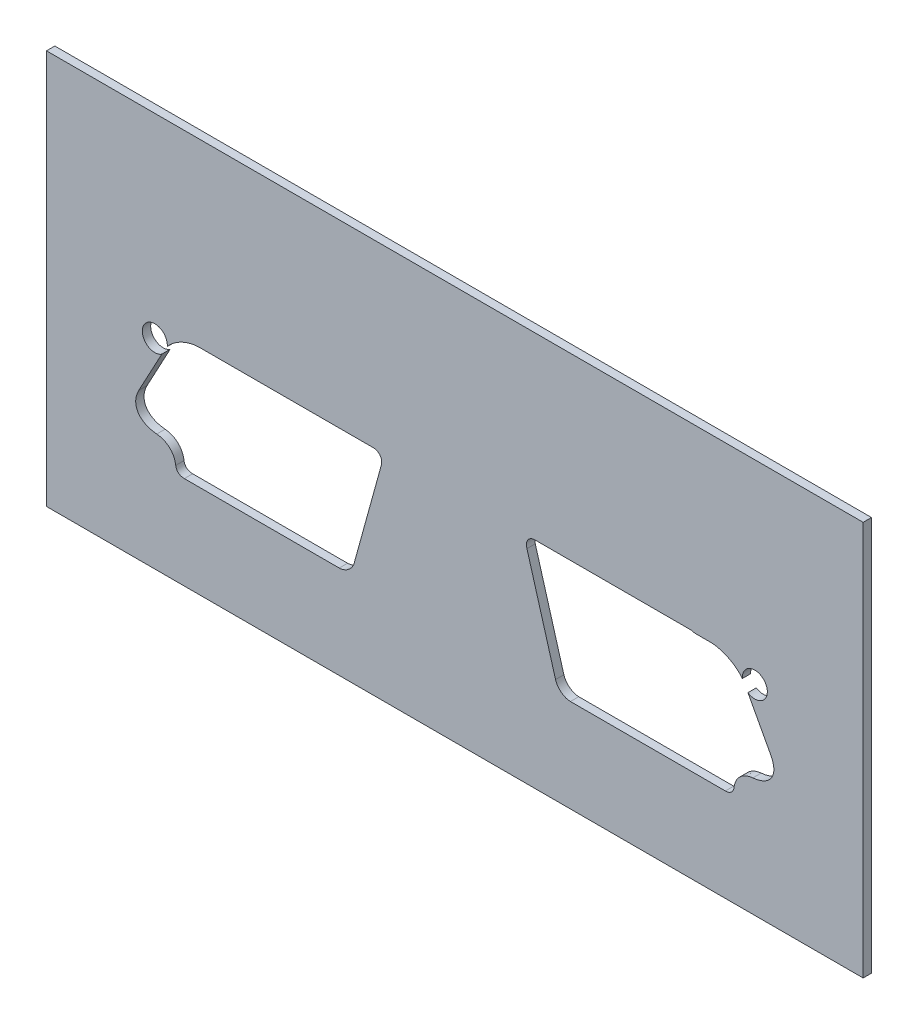
SolidWorks part; units mm, degrees
ref_plane "Спереди" through (0, 0, 0) normal (0, 0, 1) x (1, 0, 0)
ref_plane "Сверху" through (0, 0, 0) normal (0, 1, 0) x (1, 0, 0)
ref_plane "Справа" through (0, 0, 0) normal (1, 0, 0) x (0, 0, -1)
sketch "Эскиз1" plane through (0, 0, 0) normal (0, 0, 1) x (1, 0, 0)
  line L1 (-49, 5.8392) -> (-49, -22.5167)
  line L2 (-49, -22.5167) -> (49, -22.5167)
  line L3 (49, 5.8392) -> (49, -22.5167)
  line L6 (49, 26.4822) -> (49, 5.1962) construction
  line L8 (-49, 5.8392) -> (-49, 15.8392)
  line L9 (-49, 15.8392) -> (49, 15.8392)
  line L10 (49, 5.8392) -> (49, 15.8392)
extrude "Бобышка-Вытянуть1" add sketch "Эскиз1" along normal blind 1
sketch "Эскиз2" plane through (0, 0, 0) normal (0, 0, -1) x (-1, 0, 0)
  line L0 (27.2261, -9.1221) -> (15.7399, -9.1221)
  line L1 (14.9178, -10.1567) -> (17.4421, -18.9309)
  line L2 (19.1226, -20.331) -> (30.8268, -20.331)
  line L3 (31.6433, -19.2954) -> (29.101, -10.4886)
  line L4 (0, 0) -> (0, -19.7017) construction
  line L5 (-31.6433, -19.2954) -> (-29.101, -10.4886)
  line L6 (-19.1226, -20.331) -> (-30.8268, -20.331)
  line L7 (-14.9178, -10.1567) -> (-17.4421, -18.9309)
  line L8 (-27.2261, -9.1221) -> (-15.7399, -9.1221)
  arc A0 (15.7399, -9.1221) -> (14.9178, -10.1567) centre (15.8146, -10.0254) ccw
  arc A1 (17.4421, -18.9309) -> (19.1226, -20.331) centre (19.2232, -18.5017) ccw
  arc A2 (30.8268, -20.331) -> (31.6433, -19.2954) centre (30.7494, -19.4304) ccw
  arc A3 (29.101, -10.4886) -> (27.2261, -9.1221) centre (27.3312, -10.9473) ccw
  arc A4 (-29.101, -10.4886) -> (-27.2261, -9.1221) centre (-27.3312, -10.9473) cw
  arc A5 (-30.8268, -20.331) -> (-31.6433, -19.2954) centre (-30.7494, -19.4304) cw
  arc A6 (-17.4421, -18.9309) -> (-19.1226, -20.331) centre (-19.2232, -18.5017) cw
  arc A7 (-15.7399, -9.1221) -> (-14.9178, -10.1567) centre (-15.8146, -10.0254) cw
extrude "Вырез-Вытянуть4" cut sketch "Эскиз2" against normal through all
sketch "Эскиз4" plane through (0, 0, 0) normal (0, 0, -1) x (-1, 0, 0)
  circle A0 centre (36, -7.525) radius 1.5
  circle A1 centre (-36, -7.525) radius 1.5
extrude "Вырез-Вытянуть5" cut sketch "Эскиз4" against normal through all
sketch "Sketch3" plane through (0, 0, 1) normal (0, 0, 1) x (1, 0, 0)
  line L4 (-35.1709, -8.775) -> (-37.9251, -13.9067)
  line L5 (8.6523, -7.0681) -> (12.0857, -18.9615)
  line L6 (28.2287, -5.6825) -> (9.638, -5.6825)
  line L7 (30.6309, -5.7832) -> (28.7783, -5.7839)
  line L8 (37.9106, -13.8798) -> (35.1709, -8.775)
  line L9 (13.8713, -20.3472) -> (32.462, -20.3472)
  line L10 (8.6523, -7.0681) -> (12.0857, -18.9615)
  line L11 (28.2287, -5.6825) -> (9.638, -5.6825)
  line L12 (30.6309, -5.7832) -> (28.7783, -5.7839)
  line L13 (37.9106, -13.8798) -> (35.1709, -8.775)
  line L14 (13.8713, -20.3472) -> (32.462, -20.3472)
  line L15 (-9.8219, -5.7989) -> (-30.645, -5.807)
  line L16 (-12.0807, -18.9439) -> (-8.8308, -7.1669)
  line L17 (-32.462, -20.3472) -> (-13.8713, -20.3472)
  line L18 (-35.1709, -8.775) -> (-37.9251, -13.9067)
  line L19 (-9.8219, -5.7989) -> (-30.645, -5.807)
  line L20 (-12.0807, -18.9439) -> (-8.8308, -7.1669)
  line L21 (-32.462, -20.3472) -> (-13.8713, -20.3472)
  arc A2 (34.5043, -7.6389) -> (34.5716, -7.9829) centre (36, -7.525) ccw
  arc A3 (34.5716, -7.9829) -> (35.1709, -8.775) centre (36, -7.525) ccw
  arc A4 (34.5043, -7.6389) -> (34.5716, -7.9829) centre (36, -7.525) ccw
  arc A5 (34.5716, -7.9829) -> (35.1709, -8.775) centre (36, -7.525) ccw
  arc A6 (-35.1709, -8.775) -> (-34.5791, -8.0058) centre (-36, -7.525) ccw
  arc A7 (-34.5791, -8.0058) -> (-34.5051, -7.6482) centre (-36, -7.525) ccw
  arc A8 (-35.1709, -8.775) -> (-34.5791, -8.0058) centre (-36, -7.525) ccw
  arc A9 (-34.5791, -8.0058) -> (-34.5051, -7.6482) centre (-36, -7.525) ccw
  ellipse E5 centre (10.038, -7.0681) end of major axis (8.8285, -6.0207) minor radius 1.2 (9.638, -5.6825) -> (8.6523, -7.0681) ccw
  ellipse E6 centre (28.6287, -7.0681) end of major axis (27.4192, -6.0207) minor radius 1.2 (28.7783, -5.7839) -> (28.2287, -5.6825) ccw
  ellipse E7 centre (31.8702, -8.0919) end of major axis (28.7995, -6.6629) minor radius 2 (34.5043, -7.6389) -> (30.6309, -5.7832) ccw
  ellipse E8 centre (32.062, -18.9615) end of major axis (30.8525, -17.9141) minor radius 1.2 (32.462, -20.3472) -> (33.4962, -19.4843) ccw
  ellipse E9 centre (13.4713, -18.9615) end of major axis (12.2618, -17.9141) minor radius 1.2 (12.0857, -18.9615) -> (13.8713, -20.3472) ccw
  ellipse E10 centre (10.038, -7.0681) end of major axis (8.8285, -6.0207) minor radius 1.2 (9.638, -5.6825) -> (8.6523, -7.0681) ccw
  ellipse E11 centre (28.6287, -7.0681) end of major axis (27.4192, -6.0207) minor radius 1.2 (28.7783, -5.7839) -> (28.2287, -5.6825) ccw
  ellipse E12 centre (31.8702, -8.0919) end of major axis (28.7995, -6.6629) minor radius 2 (34.5043, -7.6389) -> (30.6309, -5.7832) ccw
  ellipse E13 centre (32.062, -18.9615) end of major axis (30.8525, -17.9141) minor radius 1.2 (32.462, -20.3472) -> (33.4962, -19.4843) ccw
  ellipse E14 centre (13.4713, -18.9615) end of major axis (12.2618, -17.9141) minor radius 1.2 (12.0857, -18.9615) -> (13.8713, -20.3472) ccw
  ellipse E15 centre (-31.8835, -8.1166) end of major axis (-28.8122, -6.6856) minor radius 2 (-30.645, -5.807) -> (-34.5051, -7.6482) ccw
  ellipse E16 centre (-10.2214, -7.1846) end of major axis (-9.0119, -6.1371) minor radius 1.2 (-8.8308, -7.1669) -> (-9.8219, -5.7989) ccw
  ellipse E17 centre (-13.4713, -18.9615) end of major axis (-12.2618, -17.9141) minor radius 1.2 (-13.8713, -20.3472) -> (-12.0807, -18.9439) ccw
  ellipse E18 centre (-32.062, -18.9615) end of major axis (-30.8525, -17.9141) minor radius 1.2 (-33.4952, -19.4922) -> (-32.462, -20.3472) ccw
  ellipse E19 centre (-37.0781, -20.8189) end of major axis (-34.0544, -18.2003) minor radius 3 (-33.4952, -19.4922) -> (-35.7663, -17.3693) ccw
  ellipse E20 centre (-31.8835, -8.1166) end of major axis (-28.8122, -6.6856) minor radius 2 (-30.645, -5.807) -> (-34.5051, -7.6482) ccw
  ellipse E21 centre (-10.2214, -7.1846) end of major axis (-9.0119, -6.1371) minor radius 1.2 (-8.8308, -7.1669) -> (-9.8219, -5.7989) ccw
  ellipse E22 centre (-13.4713, -18.9615) end of major axis (-12.2618, -17.9141) minor radius 1.2 (-13.8713, -20.3472) -> (-12.0807, -18.9439) ccw
  ellipse E23 centre (-32.062, -18.9615) end of major axis (-30.8525, -17.9141) minor radius 1.2 (-33.4952, -19.4922) -> (-32.462, -20.3472) ccw
  ellipse E24 centre (-37.0781, -20.8189) end of major axis (-34.0544, -18.2003) minor radius 3 (-33.4952, -19.4922) -> (-35.7663, -17.3693) ccw
  spline S1 degree 3 poles (-3612.3196, -1806.8838) (141.1066, -20.6987) (-32.5994, 3.1691) (-38.2359, -14.6873) (-38.2784, -14.8959) (-38.2974, -15.2122) (-38.2963, -15.3175) (-38.2774, -15.5276) (-38.2593, -15.6333) (-38.206, -15.8369) (-38.1708, -15.9356) (-38.0829, -16.1267) (-38.0295, -16.2198) (-37.8491, -16.4795) (-37.6989, -16.6311) (-37.3628, -16.8865) (-37.1797, -16.9895) (-17.2345, -25.642) (53.9483, 176.5986) (-943.5135, -3912.4154) knots -10.923116 -10.923116 -10.923116 -10.923116 0.125 0.125 0.25 0.25 0.3125 0.3125 0.375 0.375 0.4375 0.4375 0.5 0.5 0.625 0.625 0.75 0.75 13.437928 13.437928 13.437928 13.437928 only from (-37.9251, -13.9067) to (-35.7663, -17.3693)
  spline S2 degree 3 poles (2061.9964, -3465.9377) (-69.0178, 170.9177) (17.3944, -25.618) (37.1704, -16.959) (37.355, -16.8543) (37.6875, -16.5998) (37.8383, -16.4466) (38.0766, -16.1015) (38.1662, -15.9056) (38.2715, -15.4997) (38.2888, -15.2855) (38.2633, -14.8675) (38.2207, -14.6579) (31.82, 5.5764) (-180.6478, -51.2528) (3762.9572, 1441.6708) knots -12.455389 -12.455389 -12.455389 -12.455389 0.25 0.25 0.375 0.375 0.5 0.5 0.625 0.625 0.75 0.75 0.875 0.875 13.404708 13.404708 13.404708 13.404708 only from (35.7615, -17.3421) to (37.9106, -13.8798)
  spline S3 degree 3 poles (203.5774, 3973.3026) (187.7595, -140.5035) (26.2256, -34.1242) (33.8533, -18.4172) (34.0253, -18.1839) (34.4362, -17.8036) (34.6819, -17.6499) (51.4194, -10.709) (148.6693, -173.0193) (-3938.8197, 407.6381) knots -15.007963 -15.007963 -15.007963 -15.007963 0.25 0.25 0.5 0.5 0.75 0.75 16.651429 16.651429 16.651429 16.651429 only from (33.4962, -19.4843) to (35.7615, -17.3421)
  spline S4 degree 3 poles (35.7615, -17.3421) (36.1812, -17.3014) (36.5924, -17.2121) (37.1704, -16.959) (37.355, -16.8543) (37.6875, -16.5998) (37.8383, -16.4466) (38.0766, -16.1015) (38.1662, -15.9056) (38.2715, -15.4997) (38.2888, -15.2855) (38.2633, -14.8675) (38.2207, -14.6579) (38.0943, -14.2582) (38.0105, -14.066) (37.9106, -13.8798) knots 0 0 0 0 0.25 0.25 0.375 0.375 0.5 0.5 0.625 0.625 0.75 0.75 0.875 0.875 1 1 1 1
  spline S5 degree 3 poles (33.4962, -19.4843) (33.5297, -19.2012) (33.6073, -18.9236) (33.8533, -18.4172) (34.0253, -18.1839) (34.4362, -17.8036) (34.6819, -17.6499) (35.2, -17.4351) (35.4791, -17.3694) (35.7615, -17.3421) knots 0 0 0 0 0.25 0.25 0.5 0.5 0.75 0.75 1 1 1 1
  spline S6 degree 3 poles (-37.9251, -13.9067) (-38.0252, -14.0933) (-38.1098, -14.2878) (-38.2359, -14.6873) (-38.2784, -14.8959) (-38.2974, -15.2122) (-38.2963, -15.3175) (-38.2774, -15.5276) (-38.2593, -15.6333) (-38.206, -15.8369) (-38.1708, -15.9356) (-38.0829, -16.1267) (-38.0295, -16.2198) (-37.8491, -16.4795) (-37.6989, -16.6311) (-37.3628, -16.8865) (-37.1797, -16.9895) (-36.5959, -17.2427) (-36.1868, -17.3297) (-35.7663, -17.3693) knots 0 0 0 0 0.125 0.125 0.25 0.25 0.3125 0.3125 0.375 0.375 0.4375 0.4375 0.5 0.5 0.625 0.625 0.75 0.75 1 1 1 1
  dimension "D1" = 0
  dimension "D2" = 0
extrude "Cut-Extrude1" cut sketch "Sketch3" against normal up to surface (1 mm away) up to face at (-37.5, -7.525, 0)
sketch "Sketch4" plane through (0, 0, 1) normal (0, 0, 1) x (1, 0, 0)
  line L0 (49, -22.5167) -> (49, 15.8392) construction
  line L1 (-49, -22.5167) -> (49, -22.5167)
  line L2 (-49, -22.5167) -> (-49, -31.5167)
  line L3 (-49, -31.5167) -> (49, -31.5167)
  line L4 (49, -22.5167) -> (49, -31.5167)
  dimension "D1" = 0
  dimension "D2" = 9
extrude "Boss-Extrude1" add sketch "Sketch4" against normal blind 1
